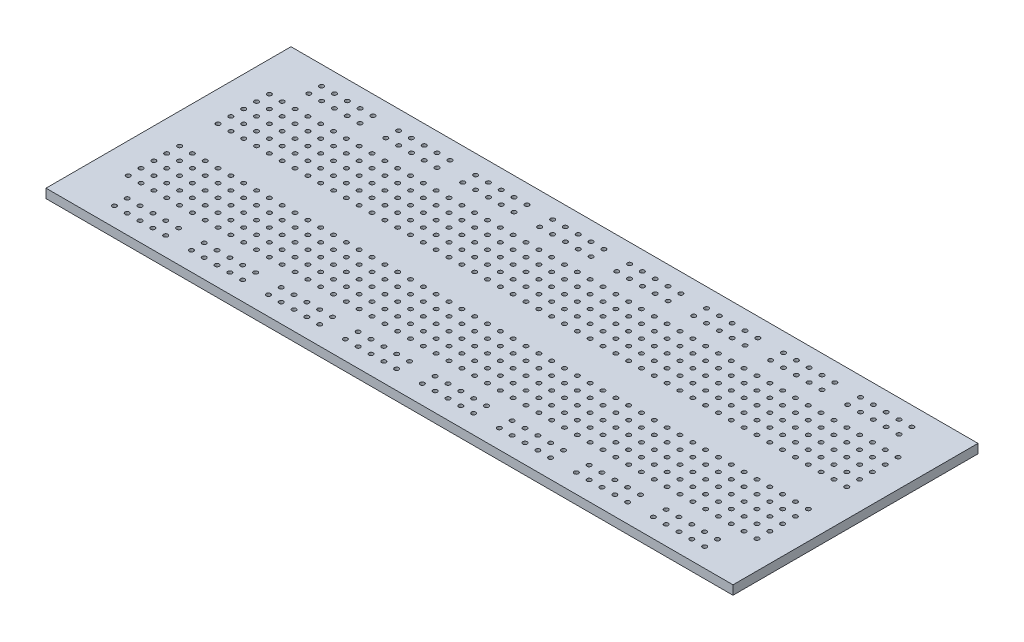
SolidWorks part; units mm, degrees
ref_plane "Alzado" through (0, 0, 0) normal (0, 0, 1) x (1, 0, 0)
ref_plane "Planta" through (0, 0, 0) normal (0, 1, 0) x (1, 0, 0)
ref_plane "Vista lateral" through (0, 0, 0) normal (1, 0, 0) x (0, 0, -1)
sketch "Croquis1" plane through (0, 0, 0) normal (0, 1, 0) x (1, 0, 0)
  line L0 (0, 24.25) -> (136, 24.25) construction
  line L1 (0, 0) -> (136, 0)
  line L2 (0, 0) -> (0, 48.5)
  line L3 (0, 48.5) -> (136, 48.5)
  line L4 (136, 0) -> (136, 48.5)
  circle A0 centre (6, 28.06) radius 0.425
  circle A5 centre (8.54, 28.06) radius 0.425
  circle A6 centre (11.08, 28.06) radius 0.425
  circle A7 centre (13.62, 28.06) radius 0.425
  circle A8 centre (16.16, 28.06) radius 0.425
  circle A9 centre (18.7, 28.06) radius 0.425
  circle A10 centre (21.24, 28.06) radius 0.425
  circle A11 centre (23.78, 28.06) radius 0.425
  circle A12 centre (26.32, 28.06) radius 0.425
  circle A13 centre (28.86, 28.06) radius 0.425
  circle A14 centre (31.4, 28.06) radius 0.425
  circle A15 centre (33.94, 28.06) radius 0.425
  circle A16 centre (36.48, 28.06) radius 0.425
  circle A17 centre (39.02, 28.06) radius 0.425
  circle A18 centre (41.56, 28.06) radius 0.425
  circle A19 centre (44.1, 28.06) radius 0.425
  circle A20 centre (46.64, 28.06) radius 0.425
  circle A21 centre (49.18, 28.06) radius 0.425
  circle A22 centre (51.72, 28.06) radius 0.425
  circle A23 centre (54.26, 28.06) radius 0.425
  circle A24 centre (56.8, 28.06) radius 0.425
  circle A25 centre (59.34, 28.06) radius 0.425
  circle A26 centre (61.88, 28.06) radius 0.425
  circle A27 centre (64.42, 28.06) radius 0.425
  circle A28 centre (66.96, 28.06) radius 0.425
  circle A29 centre (69.5, 28.06) radius 0.425
  circle A30 centre (72.04, 28.06) radius 0.425
  circle A31 centre (74.58, 28.06) radius 0.425
  circle A32 centre (77.12, 28.06) radius 0.425
  circle A33 centre (79.66, 28.06) radius 0.425
  circle A34 centre (82.2, 28.06) radius 0.425
  circle A35 centre (84.74, 28.06) radius 0.425
  circle A36 centre (87.28, 28.06) radius 0.425
  circle A37 centre (89.82, 28.06) radius 0.425
  circle A38 centre (92.36, 28.06) radius 0.425
  circle A39 centre (94.9, 28.06) radius 0.425
  circle A40 centre (97.44, 28.06) radius 0.425
  circle A41 centre (99.98, 28.06) radius 0.425
  circle A42 centre (102.52, 28.06) radius 0.425
  circle A43 centre (105.06, 28.06) radius 0.425
  circle A44 centre (107.6, 28.06) radius 0.425
  circle A45 centre (110.14, 28.06) radius 0.425
  circle A46 centre (112.68, 28.06) radius 0.425
  circle A47 centre (115.22, 28.06) radius 0.425
  circle A48 centre (117.76, 28.06) radius 0.425
  circle A49 centre (120.3, 28.06) radius 0.425
  circle A50 centre (122.84, 28.06) radius 0.425
  circle A51 centre (125.38, 28.06) radius 0.425
  circle A52 centre (127.92, 28.06) radius 0.425
  circle A53 centre (130.46, 28.06) radius 0.425
  circle A54 centre (8.54, 30.6) radius 0.425
  circle A55 centre (11.08, 30.6) radius 0.425
  circle A56 centre (13.62, 30.6) radius 0.425
  circle A57 centre (16.16, 30.6) radius 0.425
  circle A58 centre (18.7, 30.6) radius 0.425
  circle A59 centre (21.24, 30.6) radius 0.425
  circle A60 centre (23.78, 30.6) radius 0.425
  circle A61 centre (26.32, 30.6) radius 0.425
  circle A62 centre (28.86, 30.6) radius 0.425
  circle A63 centre (31.4, 30.6) radius 0.425
  circle A64 centre (33.94, 30.6) radius 0.425
  circle A65 centre (36.48, 30.6) radius 0.425
  circle A66 centre (39.02, 30.6) radius 0.425
  circle A67 centre (41.56, 30.6) radius 0.425
  circle A68 centre (44.1, 30.6) radius 0.425
  circle A69 centre (46.64, 30.6) radius 0.425
  circle A70 centre (49.18, 30.6) radius 0.425
  circle A71 centre (51.72, 30.6) radius 0.425
  circle A72 centre (54.26, 30.6) radius 0.425
  circle A73 centre (56.8, 30.6) radius 0.425
  circle A74 centre (59.34, 30.6) radius 0.425
  circle A75 centre (61.88, 30.6) radius 0.425
  circle A76 centre (64.42, 30.6) radius 0.425
  circle A77 centre (66.96, 30.6) radius 0.425
  circle A78 centre (69.5, 30.6) radius 0.425
  circle A79 centre (72.04, 30.6) radius 0.425
  circle A80 centre (74.58, 30.6) radius 0.425
  circle A81 centre (77.12, 30.6) radius 0.425
  circle A82 centre (79.66, 30.6) radius 0.425
  circle A83 centre (82.2, 30.6) radius 0.425
  circle A84 centre (84.74, 30.6) radius 0.425
  circle A85 centre (87.28, 30.6) radius 0.425
  circle A86 centre (89.82, 30.6) radius 0.425
  circle A87 centre (92.36, 30.6) radius 0.425
  circle A88 centre (94.9, 30.6) radius 0.425
  circle A89 centre (97.44, 30.6) radius 0.425
  circle A90 centre (99.98, 30.6) radius 0.425
  circle A91 centre (102.52, 30.6) radius 0.425
  circle A92 centre (105.06, 30.6) radius 0.425
  circle A93 centre (107.6, 30.6) radius 0.425
  circle A94 centre (110.14, 30.6) radius 0.425
  circle A95 centre (112.68, 30.6) radius 0.425
  circle A96 centre (115.22, 30.6) radius 0.425
  circle A97 centre (117.76, 30.6) radius 0.425
  circle A98 centre (120.3, 30.6) radius 0.425
  circle A99 centre (122.84, 30.6) radius 0.425
  circle A100 centre (125.38, 30.6) radius 0.425
  circle A101 centre (127.92, 30.6) radius 0.425
  circle A102 centre (130.46, 30.6) radius 0.425
  circle A103 centre (8.54, 33.14) radius 0.425
  circle A104 centre (11.08, 33.14) radius 0.425
  circle A105 centre (13.62, 33.14) radius 0.425
  circle A106 centre (16.16, 33.14) radius 0.425
  circle A107 centre (18.7, 33.14) radius 0.425
  circle A108 centre (21.24, 33.14) radius 0.425
  circle A109 centre (23.78, 33.14) radius 0.425
  circle A110 centre (26.32, 33.14) radius 0.425
  circle A111 centre (28.86, 33.14) radius 0.425
  circle A112 centre (31.4, 33.14) radius 0.425
  circle A113 centre (33.94, 33.14) radius 0.425
  circle A114 centre (36.48, 33.14) radius 0.425
  circle A115 centre (39.02, 33.14) radius 0.425
  circle A116 centre (41.56, 33.14) radius 0.425
  circle A117 centre (44.1, 33.14) radius 0.425
  circle A118 centre (46.64, 33.14) radius 0.425
  circle A119 centre (49.18, 33.14) radius 0.425
  circle A120 centre (51.72, 33.14) radius 0.425
  circle A121 centre (54.26, 33.14) radius 0.425
  circle A122 centre (56.8, 33.14) radius 0.425
  circle A123 centre (59.34, 33.14) radius 0.425
  circle A124 centre (61.88, 33.14) radius 0.425
  circle A125 centre (64.42, 33.14) radius 0.425
  circle A126 centre (66.96, 33.14) radius 0.425
  circle A127 centre (69.5, 33.14) radius 0.425
  circle A128 centre (72.04, 33.14) radius 0.425
  circle A129 centre (74.58, 33.14) radius 0.425
  circle A130 centre (77.12, 33.14) radius 0.425
  circle A131 centre (79.66, 33.14) radius 0.425
  circle A132 centre (82.2, 33.14) radius 0.425
  circle A133 centre (84.74, 33.14) radius 0.425
  circle A134 centre (87.28, 33.14) radius 0.425
  circle A135 centre (89.82, 33.14) radius 0.425
  circle A136 centre (92.36, 33.14) radius 0.425
  circle A137 centre (94.9, 33.14) radius 0.425
  circle A138 centre (97.44, 33.14) radius 0.425
  circle A139 centre (99.98, 33.14) radius 0.425
  circle A140 centre (102.52, 33.14) radius 0.425
  circle A141 centre (105.06, 33.14) radius 0.425
  circle A142 centre (107.6, 33.14) radius 0.425
  circle A143 centre (110.14, 33.14) radius 0.425
  circle A144 centre (112.68, 33.14) radius 0.425
  circle A145 centre (115.22, 33.14) radius 0.425
  circle A146 centre (117.76, 33.14) radius 0.425
  circle A147 centre (120.3, 33.14) radius 0.425
  circle A148 centre (122.84, 33.14) radius 0.425
  circle A149 centre (125.38, 33.14) radius 0.425
  circle A150 centre (127.92, 33.14) radius 0.425
  circle A151 centre (130.46, 33.14) radius 0.425
  circle A152 centre (8.54, 35.68) radius 0.425
  circle A153 centre (11.08, 35.68) radius 0.425
  circle A154 centre (13.62, 35.68) radius 0.425
  circle A155 centre (16.16, 35.68) radius 0.425
  circle A156 centre (18.7, 35.68) radius 0.425
  circle A157 centre (21.24, 35.68) radius 0.425
  circle A158 centre (23.78, 35.68) radius 0.425
  circle A159 centre (26.32, 35.68) radius 0.425
  circle A160 centre (28.86, 35.68) radius 0.425
  circle A161 centre (31.4, 35.68) radius 0.425
  circle A162 centre (33.94, 35.68) radius 0.425
  circle A163 centre (36.48, 35.68) radius 0.425
  circle A164 centre (39.02, 35.68) radius 0.425
  circle A165 centre (41.56, 35.68) radius 0.425
  circle A166 centre (44.1, 35.68) radius 0.425
  circle A167 centre (46.64, 35.68) radius 0.425
  circle A168 centre (49.18, 35.68) radius 0.425
  circle A169 centre (51.72, 35.68) radius 0.425
  circle A170 centre (54.26, 35.68) radius 0.425
  circle A171 centre (56.8, 35.68) radius 0.425
  circle A172 centre (59.34, 35.68) radius 0.425
  circle A173 centre (61.88, 35.68) radius 0.425
  circle A174 centre (64.42, 35.68) radius 0.425
  circle A175 centre (66.96, 35.68) radius 0.425
  circle A176 centre (69.5, 35.68) radius 0.425
  circle A177 centre (72.04, 35.68) radius 0.425
  circle A178 centre (74.58, 35.68) radius 0.425
  circle A179 centre (77.12, 35.68) radius 0.425
  circle A180 centre (79.66, 35.68) radius 0.425
  circle A181 centre (82.2, 35.68) radius 0.425
  circle A182 centre (84.74, 35.68) radius 0.425
  circle A183 centre (87.28, 35.68) radius 0.425
  circle A184 centre (89.82, 35.68) radius 0.425
  circle A185 centre (92.36, 35.68) radius 0.425
  circle A186 centre (94.9, 35.68) radius 0.425
  circle A187 centre (97.44, 35.68) radius 0.425
  circle A188 centre (99.98, 35.68) radius 0.425
  circle A189 centre (102.52, 35.68) radius 0.425
  circle A190 centre (105.06, 35.68) radius 0.425
  circle A191 centre (107.6, 35.68) radius 0.425
  circle A192 centre (110.14, 35.68) radius 0.425
  circle A193 centre (112.68, 35.68) radius 0.425
  circle A194 centre (115.22, 35.68) radius 0.425
  circle A195 centre (117.76, 35.68) radius 0.425
  circle A196 centre (120.3, 35.68) radius 0.425
  circle A197 centre (122.84, 35.68) radius 0.425
  circle A198 centre (125.38, 35.68) radius 0.425
  circle A199 centre (127.92, 35.68) radius 0.425
  circle A200 centre (130.46, 35.68) radius 0.425
  circle A201 centre (8.54, 38.22) radius 0.425
  circle A202 centre (11.08, 38.22) radius 0.425
  circle A203 centre (13.62, 38.22) radius 0.425
  circle A204 centre (16.16, 38.22) radius 0.425
  circle A205 centre (18.7, 38.22) radius 0.425
  circle A206 centre (21.24, 38.22) radius 0.425
  circle A207 centre (23.78, 38.22) radius 0.425
  circle A208 centre (26.32, 38.22) radius 0.425
  circle A209 centre (28.86, 38.22) radius 0.425
  circle A210 centre (31.4, 38.22) radius 0.425
  circle A211 centre (33.94, 38.22) radius 0.425
  circle A212 centre (36.48, 38.22) radius 0.425
  circle A213 centre (39.02, 38.22) radius 0.425
  circle A214 centre (41.56, 38.22) radius 0.425
  circle A215 centre (44.1, 38.22) radius 0.425
  circle A216 centre (46.64, 38.22) radius 0.425
  circle A217 centre (49.18, 38.22) radius 0.425
  circle A218 centre (51.72, 38.22) radius 0.425
  circle A219 centre (54.26, 38.22) radius 0.425
  circle A220 centre (56.8, 38.22) radius 0.425
  circle A221 centre (59.34, 38.22) radius 0.425
  circle A222 centre (61.88, 38.22) radius 0.425
  circle A223 centre (64.42, 38.22) radius 0.425
  circle A224 centre (66.96, 38.22) radius 0.425
  circle A225 centre (69.5, 38.22) radius 0.425
  circle A226 centre (72.04, 38.22) radius 0.425
  circle A227 centre (74.58, 38.22) radius 0.425
  circle A228 centre (77.12, 38.22) radius 0.425
  circle A229 centre (79.66, 38.22) radius 0.425
  circle A230 centre (82.2, 38.22) radius 0.425
  circle A231 centre (84.74, 38.22) radius 0.425
  circle A232 centre (87.28, 38.22) radius 0.425
  circle A233 centre (89.82, 38.22) radius 0.425
  circle A234 centre (92.36, 38.22) radius 0.425
  circle A235 centre (94.9, 38.22) radius 0.425
  circle A236 centre (97.44, 38.22) radius 0.425
  circle A237 centre (99.98, 38.22) radius 0.425
  circle A238 centre (102.52, 38.22) radius 0.425
  circle A239 centre (105.06, 38.22) radius 0.425
  circle A240 centre (107.6, 38.22) radius 0.425
  circle A241 centre (110.14, 38.22) radius 0.425
  circle A242 centre (112.68, 38.22) radius 0.425
  circle A243 centre (115.22, 38.22) radius 0.425
  circle A244 centre (117.76, 38.22) radius 0.425
  circle A245 centre (120.3, 38.22) radius 0.425
  circle A246 centre (122.84, 38.22) radius 0.425
  circle A247 centre (125.38, 38.22) radius 0.425
  circle A248 centre (127.92, 38.22) radius 0.425
  circle A249 centre (130.46, 38.22) radius 0.425
  circle A250 centre (6, 30.6) radius 0.425
  circle A251 centre (6, 33.14) radius 0.425
  circle A252 centre (6, 35.68) radius 0.425
  circle A253 centre (6, 38.22) radius 0.425
  circle A254 centre (9.8, 42.22) radius 0.425
  circle A255 centre (12.34, 42.22) radius 0.425
  circle A256 centre (14.88, 42.22) radius 0.425
  circle A257 centre (17.42, 42.22) radius 0.425
  circle A258 centre (19.96, 42.22) radius 0.425
  circle A259 centre (12.34, 44.76) radius 0.425
  circle A260 centre (14.88, 44.76) radius 0.425
  circle A261 centre (17.42, 44.76) radius 0.425
  circle A262 centre (19.96, 44.76) radius 0.425
  circle A263 centre (9.8, 44.76) radius 0.425
  circle A264 centre (25.04, 44.76) radius 0.425
  circle A265 centre (27.58, 44.76) radius 0.425
  circle A266 centre (30.12, 44.76) radius 0.425
  circle A267 centre (32.66, 44.76) radius 0.425
  circle A268 centre (35.2, 44.76) radius 0.425
  circle A269 centre (35.2, 42.22) radius 0.425
  circle A270 centre (32.66, 42.22) radius 0.425
  circle A271 centre (30.12, 42.22) radius 0.425
  circle A272 centre (27.58, 42.22) radius 0.425
  circle A273 centre (25.04, 42.22) radius 0.425
  circle A274 centre (40.28, 44.76) radius 0.425
  circle A275 centre (42.82, 44.76) radius 0.425
  circle A276 centre (45.36, 44.76) radius 0.425
  circle A277 centre (47.9, 44.76) radius 0.425
  circle A278 centre (50.44, 44.76) radius 0.425
  circle A279 centre (50.44, 42.22) radius 0.425
  circle A280 centre (47.9, 42.22) radius 0.425
  circle A281 centre (45.36, 42.22) radius 0.425
  circle A282 centre (42.82, 42.22) radius 0.425
  circle A283 centre (40.28, 42.22) radius 0.425
  circle A284 centre (55.52, 44.76) radius 0.425
  circle A285 centre (58.06, 44.76) radius 0.425
  circle A286 centre (60.6, 44.76) radius 0.425
  circle A287 centre (63.14, 44.76) radius 0.425
  circle A288 centre (65.68, 44.76) radius 0.425
  circle A289 centre (65.68, 42.22) radius 0.425
  circle A290 centre (63.14, 42.22) radius 0.425
  circle A291 centre (60.6, 42.22) radius 0.425
  circle A292 centre (58.06, 42.22) radius 0.425
  circle A293 centre (55.52, 42.22) radius 0.425
  circle A294 centre (70.76, 44.76) radius 0.425
  circle A295 centre (73.3, 44.76) radius 0.425
  circle A296 centre (75.84, 44.76) radius 0.425
  circle A297 centre (78.38, 44.76) radius 0.425
  circle A298 centre (80.92, 44.76) radius 0.425
  circle A299 centre (80.92, 42.22) radius 0.425
  circle A300 centre (78.38, 42.22) radius 0.425
  circle A301 centre (75.84, 42.22) radius 0.425
  circle A302 centre (73.3, 42.22) radius 0.425
  circle A303 centre (70.76, 42.22) radius 0.425
  circle A304 centre (86, 44.76) radius 0.425
  circle A305 centre (88.54, 44.76) radius 0.425
  circle A306 centre (91.08, 44.76) radius 0.425
  circle A307 centre (93.62, 44.76) radius 0.425
  circle A308 centre (96.16, 44.76) radius 0.425
  circle A309 centre (96.16, 42.22) radius 0.425
  circle A310 centre (93.62, 42.22) radius 0.425
  circle A311 centre (91.08, 42.22) radius 0.425
  circle A312 centre (88.54, 42.22) radius 0.425
  circle A313 centre (86, 42.22) radius 0.425
  circle A314 centre (101.24, 44.76) radius 0.425
  circle A315 centre (103.78, 44.76) radius 0.425
  circle A316 centre (106.32, 44.76) radius 0.425
  circle A317 centre (108.86, 44.76) radius 0.425
  circle A318 centre (111.4, 44.76) radius 0.425
  circle A319 centre (111.4, 42.22) radius 0.425
  circle A320 centre (108.86, 42.22) radius 0.425
  circle A321 centre (106.32, 42.22) radius 0.425
  circle A322 centre (103.78, 42.22) radius 0.425
  circle A323 centre (101.24, 42.22) radius 0.425
  circle A324 centre (116.48, 44.76) radius 0.425
  circle A325 centre (119.02, 44.76) radius 0.425
  circle A326 centre (121.56, 44.76) radius 0.425
  circle A327 centre (124.1, 44.76) radius 0.425
  circle A328 centre (126.64, 44.76) radius 0.425
  circle A329 centre (126.64, 42.22) radius 0.425
  circle A330 centre (124.1, 42.22) radius 0.425
  circle A331 centre (121.56, 42.22) radius 0.425
  circle A332 centre (119.02, 42.22) radius 0.425
  circle A333 centre (116.48, 42.22) radius 0.425
  circle A334 centre (116.48, 6.28) radius 0.425
  circle A335 centre (119.02, 6.28) radius 0.425
  circle A336 centre (121.56, 6.28) radius 0.425
  circle A337 centre (124.1, 6.28) radius 0.425
  circle A338 centre (126.64, 6.28) radius 0.425
  circle A339 centre (126.64, 3.74) radius 0.425
  circle A340 centre (124.1, 3.74) radius 0.425
  circle A341 centre (121.56, 3.74) radius 0.425
  circle A342 centre (119.02, 3.74) radius 0.425
  circle A343 centre (116.48, 3.74) radius 0.425
  circle A344 centre (101.24, 6.28) radius 0.425
  circle A345 centre (103.78, 6.28) radius 0.425
  circle A346 centre (106.32, 6.28) radius 0.425
  circle A347 centre (108.86, 6.28) radius 0.425
  circle A348 centre (111.4, 6.28) radius 0.425
  circle A349 centre (111.4, 3.74) radius 0.425
  circle A350 centre (108.86, 3.74) radius 0.425
  circle A351 centre (106.32, 3.74) radius 0.425
  circle A352 centre (103.78, 3.74) radius 0.425
  circle A353 centre (101.24, 3.74) radius 0.425
  circle A354 centre (86, 6.28) radius 0.425
  circle A355 centre (88.54, 6.28) radius 0.425
  circle A356 centre (91.08, 6.28) radius 0.425
  circle A357 centre (93.62, 6.28) radius 0.425
  circle A358 centre (96.16, 6.28) radius 0.425
  circle A359 centre (96.16, 3.74) radius 0.425
  circle A360 centre (93.62, 3.74) radius 0.425
  circle A361 centre (91.08, 3.74) radius 0.425
  circle A362 centre (88.54, 3.74) radius 0.425
  circle A363 centre (86, 3.74) radius 0.425
  circle A364 centre (70.76, 6.28) radius 0.425
  circle A365 centre (73.3, 6.28) radius 0.425
  circle A366 centre (75.84, 6.28) radius 0.425
  circle A367 centre (78.38, 6.28) radius 0.425
  circle A368 centre (80.92, 6.28) radius 0.425
  circle A369 centre (80.92, 3.74) radius 0.425
  circle A370 centre (78.38, 3.74) radius 0.425
  circle A371 centre (75.84, 3.74) radius 0.425
  circle A372 centre (73.3, 3.74) radius 0.425
  circle A373 centre (70.76, 3.74) radius 0.425
  circle A374 centre (55.52, 6.28) radius 0.425
  circle A375 centre (58.06, 6.28) radius 0.425
  circle A376 centre (60.6, 6.28) radius 0.425
  circle A377 centre (63.14, 6.28) radius 0.425
  circle A378 centre (65.68, 6.28) radius 0.425
  circle A379 centre (65.68, 3.74) radius 0.425
  circle A380 centre (63.14, 3.74) radius 0.425
  circle A381 centre (60.6, 3.74) radius 0.425
  circle A382 centre (58.06, 3.74) radius 0.425
  circle A383 centre (55.52, 3.74) radius 0.425
  circle A384 centre (40.28, 6.28) radius 0.425
  circle A385 centre (42.82, 6.28) radius 0.425
  circle A386 centre (45.36, 6.28) radius 0.425
  circle A387 centre (47.9, 6.28) radius 0.425
  circle A388 centre (50.44, 6.28) radius 0.425
  circle A389 centre (50.44, 3.74) radius 0.425
  circle A390 centre (47.9, 3.74) radius 0.425
  circle A391 centre (45.36, 3.74) radius 0.425
  circle A392 centre (42.82, 3.74) radius 0.425
  circle A393 centre (40.28, 3.74) radius 0.425
  circle A394 centre (25.04, 6.28) radius 0.425
  circle A395 centre (27.58, 6.28) radius 0.425
  circle A396 centre (30.12, 6.28) radius 0.425
  circle A397 centre (32.66, 6.28) radius 0.425
  circle A398 centre (35.2, 6.28) radius 0.425
  circle A399 centre (35.2, 3.74) radius 0.425
  circle A400 centre (32.66, 3.74) radius 0.425
  circle A401 centre (30.12, 3.74) radius 0.425
  circle A402 centre (27.58, 3.74) radius 0.425
  circle A403 centre (25.04, 3.74) radius 0.425
  circle A404 centre (9.8, 3.74) radius 0.425
  circle A405 centre (19.96, 3.74) radius 0.425
  circle A406 centre (17.42, 3.74) radius 0.425
  circle A407 centre (14.88, 3.74) radius 0.425
  circle A408 centre (12.34, 3.74) radius 0.425
  circle A409 centre (19.96, 6.28) radius 0.425
  circle A410 centre (17.42, 6.28) radius 0.425
  circle A411 centre (14.88, 6.28) radius 0.425
  circle A412 centre (12.34, 6.28) radius 0.425
  circle A413 centre (9.8, 6.28) radius 0.425
  circle A414 centre (6, 10.28) radius 0.425
  circle A415 centre (6, 12.82) radius 0.425
  circle A416 centre (6, 15.36) radius 0.425
  circle A417 centre (6, 17.9) radius 0.425
  circle A418 centre (130.46, 10.28) radius 0.425
  circle A419 centre (127.92, 10.28) radius 0.425
  circle A420 centre (125.38, 10.28) radius 0.425
  circle A421 centre (122.84, 10.28) radius 0.425
  circle A422 centre (120.3, 10.28) radius 0.425
  circle A423 centre (117.76, 10.28) radius 0.425
  circle A424 centre (115.22, 10.28) radius 0.425
  circle A425 centre (112.68, 10.28) radius 0.425
  circle A426 centre (110.14, 10.28) radius 0.425
  circle A427 centre (107.6, 10.28) radius 0.425
  circle A428 centre (105.06, 10.28) radius 0.425
  circle A429 centre (102.52, 10.28) radius 0.425
  circle A430 centre (99.98, 10.28) radius 0.425
  circle A431 centre (97.44, 10.28) radius 0.425
  circle A432 centre (94.9, 10.28) radius 0.425
  circle A433 centre (92.36, 10.28) radius 0.425
  circle A434 centre (89.82, 10.28) radius 0.425
  circle A435 centre (87.28, 10.28) radius 0.425
  circle A436 centre (84.74, 10.28) radius 0.425
  circle A437 centre (82.2, 10.28) radius 0.425
  circle A438 centre (79.66, 10.28) radius 0.425
  circle A439 centre (77.12, 10.28) radius 0.425
  circle A440 centre (74.58, 10.28) radius 0.425
  circle A441 centre (72.04, 10.28) radius 0.425
  circle A442 centre (69.5, 10.28) radius 0.425
  circle A443 centre (66.96, 10.28) radius 0.425
  circle A444 centre (64.42, 10.28) radius 0.425
  circle A445 centre (61.88, 10.28) radius 0.425
  circle A446 centre (59.34, 10.28) radius 0.425
  circle A447 centre (56.8, 10.28) radius 0.425
  circle A448 centre (54.26, 10.28) radius 0.425
  circle A449 centre (51.72, 10.28) radius 0.425
  circle A450 centre (49.18, 10.28) radius 0.425
  circle A451 centre (46.64, 10.28) radius 0.425
  circle A452 centre (44.1, 10.28) radius 0.425
  circle A453 centre (41.56, 10.28) radius 0.425
  circle A454 centre (39.02, 10.28) radius 0.425
  circle A455 centre (36.48, 10.28) radius 0.425
  circle A456 centre (33.94, 10.28) radius 0.425
  circle A457 centre (31.4, 10.28) radius 0.425
  circle A458 centre (28.86, 10.28) radius 0.425
  circle A459 centre (26.32, 10.28) radius 0.425
  circle A460 centre (23.78, 10.28) radius 0.425
  circle A461 centre (21.24, 10.28) radius 0.425
  circle A462 centre (18.7, 10.28) radius 0.425
  circle A463 centre (16.16, 10.28) radius 0.425
  circle A464 centre (13.62, 10.28) radius 0.425
  circle A465 centre (11.08, 10.28) radius 0.425
  circle A466 centre (8.54, 10.28) radius 0.425
  circle A467 centre (130.46, 12.82) radius 0.425
  circle A468 centre (127.92, 12.82) radius 0.425
  circle A469 centre (125.38, 12.82) radius 0.425
  circle A470 centre (122.84, 12.82) radius 0.425
  circle A471 centre (120.3, 12.82) radius 0.425
  circle A472 centre (117.76, 12.82) radius 0.425
  circle A473 centre (115.22, 12.82) radius 0.425
  circle A474 centre (112.68, 12.82) radius 0.425
  circle A475 centre (110.14, 12.82) radius 0.425
  circle A476 centre (107.6, 12.82) radius 0.425
  circle A477 centre (105.06, 12.82) radius 0.425
  circle A478 centre (102.52, 12.82) radius 0.425
  circle A479 centre (99.98, 12.82) radius 0.425
  circle A480 centre (97.44, 12.82) radius 0.425
  circle A481 centre (94.9, 12.82) radius 0.425
  circle A482 centre (92.36, 12.82) radius 0.425
  circle A483 centre (89.82, 12.82) radius 0.425
  circle A484 centre (87.28, 12.82) radius 0.425
  circle A485 centre (84.74, 12.82) radius 0.425
  circle A486 centre (82.2, 12.82) radius 0.425
  circle A487 centre (79.66, 12.82) radius 0.425
  circle A488 centre (77.12, 12.82) radius 0.425
  circle A489 centre (74.58, 12.82) radius 0.425
  circle A490 centre (72.04, 12.82) radius 0.425
  circle A491 centre (69.5, 12.82) radius 0.425
  circle A492 centre (66.96, 12.82) radius 0.425
  circle A493 centre (64.42, 12.82) radius 0.425
  circle A494 centre (61.88, 12.82) radius 0.425
  circle A495 centre (59.34, 12.82) radius 0.425
  circle A496 centre (56.8, 12.82) radius 0.425
  circle A497 centre (54.26, 12.82) radius 0.425
  circle A498 centre (51.72, 12.82) radius 0.425
  circle A499 centre (49.18, 12.82) radius 0.425
  circle A500 centre (46.64, 12.82) radius 0.425
  circle A501 centre (44.1, 12.82) radius 0.425
  circle A502 centre (41.56, 12.82) radius 0.425
  circle A503 centre (39.02, 12.82) radius 0.425
  circle A504 centre (36.48, 12.82) radius 0.425
  circle A505 centre (33.94, 12.82) radius 0.425
  circle A506 centre (31.4, 12.82) radius 0.425
  circle A507 centre (28.86, 12.82) radius 0.425
  circle A508 centre (26.32, 12.82) radius 0.425
  circle A509 centre (23.78, 12.82) radius 0.425
  circle A510 centre (21.24, 12.82) radius 0.425
  circle A511 centre (18.7, 12.82) radius 0.425
  circle A512 centre (16.16, 12.82) radius 0.425
  circle A513 centre (13.62, 12.82) radius 0.425
  circle A514 centre (11.08, 12.82) radius 0.425
  circle A515 centre (8.54, 12.82) radius 0.425
  circle A516 centre (130.46, 15.36) radius 0.425
  circle A517 centre (127.92, 15.36) radius 0.425
  circle A518 centre (125.38, 15.36) radius 0.425
  circle A519 centre (122.84, 15.36) radius 0.425
  circle A520 centre (120.3, 15.36) radius 0.425
  circle A521 centre (117.76, 15.36) radius 0.425
  circle A522 centre (115.22, 15.36) radius 0.425
  circle A523 centre (112.68, 15.36) radius 0.425
  circle A524 centre (110.14, 15.36) radius 0.425
  circle A525 centre (107.6, 15.36) radius 0.425
  circle A526 centre (105.06, 15.36) radius 0.425
  circle A527 centre (102.52, 15.36) radius 0.425
  circle A528 centre (99.98, 15.36) radius 0.425
  circle A529 centre (97.44, 15.36) radius 0.425
  circle A530 centre (94.9, 15.36) radius 0.425
  circle A531 centre (92.36, 15.36) radius 0.425
  circle A532 centre (89.82, 15.36) radius 0.425
  circle A533 centre (87.28, 15.36) radius 0.425
  circle A534 centre (84.74, 15.36) radius 0.425
  circle A535 centre (82.2, 15.36) radius 0.425
  circle A536 centre (79.66, 15.36) radius 0.425
  circle A537 centre (77.12, 15.36) radius 0.425
  circle A538 centre (74.58, 15.36) radius 0.425
  circle A539 centre (72.04, 15.36) radius 0.425
  circle A540 centre (69.5, 15.36) radius 0.425
  circle A541 centre (66.96, 15.36) radius 0.425
  circle A542 centre (64.42, 15.36) radius 0.425
  circle A543 centre (61.88, 15.36) radius 0.425
  circle A544 centre (59.34, 15.36) radius 0.425
  circle A545 centre (56.8, 15.36) radius 0.425
  circle A546 centre (54.26, 15.36) radius 0.425
  circle A547 centre (51.72, 15.36) radius 0.425
  circle A548 centre (49.18, 15.36) radius 0.425
  circle A549 centre (46.64, 15.36) radius 0.425
  circle A550 centre (44.1, 15.36) radius 0.425
  circle A551 centre (41.56, 15.36) radius 0.425
  circle A552 centre (39.02, 15.36) radius 0.425
  circle A553 centre (36.48, 15.36) radius 0.425
  circle A554 centre (33.94, 15.36) radius 0.425
  circle A555 centre (31.4, 15.36) radius 0.425
  circle A556 centre (28.86, 15.36) radius 0.425
  circle A557 centre (26.32, 15.36) radius 0.425
  circle A558 centre (23.78, 15.36) radius 0.425
  circle A559 centre (21.24, 15.36) radius 0.425
  circle A560 centre (18.7, 15.36) radius 0.425
  circle A561 centre (16.16, 15.36) radius 0.425
  circle A562 centre (13.62, 15.36) radius 0.425
  circle A563 centre (11.08, 15.36) radius 0.425
  circle A564 centre (8.54, 15.36) radius 0.425
  circle A565 centre (130.46, 17.9) radius 0.425
  circle A566 centre (127.92, 17.9) radius 0.425
  circle A567 centre (125.38, 17.9) radius 0.425
  circle A568 centre (122.84, 17.9) radius 0.425
  circle A569 centre (120.3, 17.9) radius 0.425
  circle A570 centre (117.76, 17.9) radius 0.425
  circle A571 centre (115.22, 17.9) radius 0.425
  circle A572 centre (112.68, 17.9) radius 0.425
  circle A573 centre (110.14, 17.9) radius 0.425
  circle A574 centre (107.6, 17.9) radius 0.425
  circle A575 centre (105.06, 17.9) radius 0.425
  circle A576 centre (102.52, 17.9) radius 0.425
  circle A577 centre (99.98, 17.9) radius 0.425
  circle A578 centre (97.44, 17.9) radius 0.425
  circle A579 centre (94.9, 17.9) radius 0.425
  circle A580 centre (92.36, 17.9) radius 0.425
  circle A581 centre (89.82, 17.9) radius 0.425
  circle A582 centre (87.28, 17.9) radius 0.425
  circle A583 centre (84.74, 17.9) radius 0.425
  circle A584 centre (82.2, 17.9) radius 0.425
  circle A585 centre (79.66, 17.9) radius 0.425
  circle A586 centre (77.12, 17.9) radius 0.425
  circle A587 centre (74.58, 17.9) radius 0.425
  circle A588 centre (72.04, 17.9) radius 0.425
  circle A589 centre (69.5, 17.9) radius 0.425
  circle A590 centre (66.96, 17.9) radius 0.425
  circle A591 centre (64.42, 17.9) radius 0.425
  circle A592 centre (61.88, 17.9) radius 0.425
  circle A593 centre (59.34, 17.9) radius 0.425
  circle A594 centre (56.8, 17.9) radius 0.425
  circle A595 centre (54.26, 17.9) radius 0.425
  circle A596 centre (51.72, 17.9) radius 0.425
  circle A597 centre (49.18, 17.9) radius 0.425
  circle A598 centre (46.64, 17.9) radius 0.425
  circle A599 centre (44.1, 17.9) radius 0.425
  circle A600 centre (41.56, 17.9) radius 0.425
  circle A601 centre (39.02, 17.9) radius 0.425
  circle A602 centre (36.48, 17.9) radius 0.425
  circle A603 centre (33.94, 17.9) radius 0.425
  circle A604 centre (31.4, 17.9) radius 0.425
  circle A605 centre (28.86, 17.9) radius 0.425
  circle A606 centre (26.32, 17.9) radius 0.425
  circle A607 centre (23.78, 17.9) radius 0.425
  circle A608 centre (21.24, 17.9) radius 0.425
  circle A609 centre (18.7, 17.9) radius 0.425
  circle A610 centre (16.16, 17.9) radius 0.425
  circle A611 centre (13.62, 17.9) radius 0.425
  circle A612 centre (11.08, 17.9) radius 0.425
  circle A613 centre (8.54, 17.9) radius 0.425
  circle A614 centre (130.46, 20.44) radius 0.425
  circle A615 centre (127.92, 20.44) radius 0.425
  circle A616 centre (125.38, 20.44) radius 0.425
  circle A617 centre (122.84, 20.44) radius 0.425
  circle A618 centre (120.3, 20.44) radius 0.425
  circle A619 centre (117.76, 20.44) radius 0.425
  circle A620 centre (115.22, 20.44) radius 0.425
  circle A621 centre (112.68, 20.44) radius 0.425
  circle A622 centre (110.14, 20.44) radius 0.425
  circle A623 centre (107.6, 20.44) radius 0.425
  circle A624 centre (105.06, 20.44) radius 0.425
  circle A625 centre (102.52, 20.44) radius 0.425
  circle A626 centre (99.98, 20.44) radius 0.425
  circle A627 centre (97.44, 20.44) radius 0.425
  circle A628 centre (94.9, 20.44) radius 0.425
  circle A629 centre (92.36, 20.44) radius 0.425
  circle A630 centre (89.82, 20.44) radius 0.425
  circle A631 centre (87.28, 20.44) radius 0.425
  circle A632 centre (84.74, 20.44) radius 0.425
  circle A633 centre (82.2, 20.44) radius 0.425
  circle A634 centre (79.66, 20.44) radius 0.425
  circle A635 centre (77.12, 20.44) radius 0.425
  circle A636 centre (74.58, 20.44) radius 0.425
  circle A637 centre (72.04, 20.44) radius 0.425
  circle A638 centre (69.5, 20.44) radius 0.425
  circle A639 centre (66.96, 20.44) radius 0.425
  circle A640 centre (64.42, 20.44) radius 0.425
  circle A641 centre (61.88, 20.44) radius 0.425
  circle A642 centre (59.34, 20.44) radius 0.425
  circle A643 centre (56.8, 20.44) radius 0.425
  circle A644 centre (54.26, 20.44) radius 0.425
  circle A645 centre (51.72, 20.44) radius 0.425
  circle A646 centre (49.18, 20.44) radius 0.425
  circle A647 centre (46.64, 20.44) radius 0.425
  circle A648 centre (44.1, 20.44) radius 0.425
  circle A649 centre (41.56, 20.44) radius 0.425
  circle A650 centre (39.02, 20.44) radius 0.425
  circle A651 centre (36.48, 20.44) radius 0.425
  circle A652 centre (33.94, 20.44) radius 0.425
  circle A653 centre (31.4, 20.44) radius 0.425
  circle A654 centre (28.86, 20.44) radius 0.425
  circle A655 centre (26.32, 20.44) radius 0.425
  circle A656 centre (23.78, 20.44) radius 0.425
  circle A657 centre (21.24, 20.44) radius 0.425
  circle A658 centre (18.7, 20.44) radius 0.425
  circle A659 centre (16.16, 20.44) radius 0.425
  circle A660 centre (13.62, 20.44) radius 0.425
  circle A661 centre (11.08, 20.44) radius 0.425
  circle A662 centre (8.54, 20.44) radius 0.425
  circle A663 centre (6, 20.44) radius 0.425
  dimension "D2" = 3.81
  dimension "D3" = 6
  dimension "D4" = 0.85
  dimension "D7" = 0.85
  dimension "D8" = 9.8
  dimension "D9" = 4
  dimension "D1" = 48.5
  dimension "136" = 136
  dimension "D5" = 50
  dimension "D6" = 5
  dimension "D10" = 5
  dimension "D11" = 2
  dimension "D12" = 8
extrude "Saliente-Extruir1" add sketch "Croquis1" along normal blind 1.8
